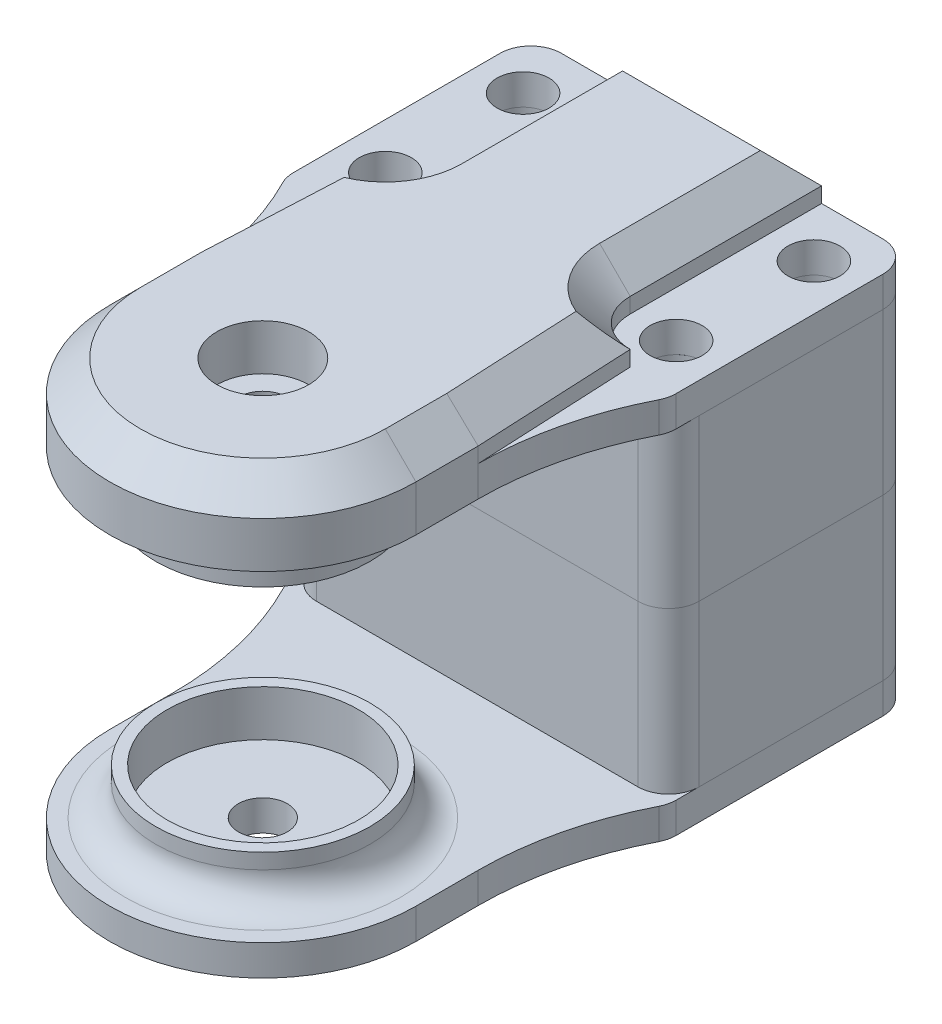
SolidWorks part; units mm, degrees
ref_plane "前视基准面" through (0, 0, 0) normal (0, 0, 1) x (1, 0, 0)
ref_plane "上视基准面" through (0, 0, 0) normal (0, 1, 0) x (1, 0, 0)
ref_plane "右视基准面" through (0, 0, 0) normal (1, 0, 0) x (0, 0, -1)
sketch "草图2" plane through (0, 0, 0) normal (0, 1, 0) x (1, 0, 0)
  circle A0 centre (0, 0) radius 10
  dimension "D1" = 20
extrude "凸台-拉伸1" add sketch "草图2" along normal blind 2
sketch "草图3" plane through (0, 2, 0) normal (0, 1, 0) x (1, 0, 0)
  line L0 (0, 8) -> (0, -8) construction
  circle A0 centre (0, 0) radius 6.25
  circle A1 centre (0, 0) radius 7
  dimension "D1" = 12.5
  dimension "D2" = 14
extrude "凸台-拉伸2" add sketch "草图3" along normal blind 3
sketch "草图4" plane through (0, 2, 0) normal (0, 1, 0) x (1, 0, 0)
  circle A0 centre (0, 0) radius 1.6
  dimension "D1" = 3.2
extrude "切除-拉伸1" cut sketch "草图4" against normal up to next
sketch "草图6" plane through (0, 0, 0) normal (0, -1, 0) x (1, 0, 0)
  line L0 (-10, 0) -> (-10, -30)
  line L1 (-10, -30) -> (10, -30)
  line L2 (10, -30) -> (10, 0)
  circle A0 centre (0, 0) radius 1.6 construction
  circle A1 centre (0, 0) radius 1.6
  circle A3 centre (0, 0) radius 10
  arc A4 (10, 0) -> (-10, 0) centre (0, 0) ccw
  dimension "D2" = 30
  dimension "D1" = 0
extrude "凸台-拉伸3" add sketch "草图6" against normal blind 2
sketch "草图11" plane through (0, 0, 0) normal (0, -1, 0) x (1, 0, 0)
  line L0 (0, -30) -> (0, -5.5094) construction
  line L1 (-10, -30) -> (10, -30) construction
  line L3 (-12.5, -14) -> (12.5, -14)
  line L4 (-12.5, -14) -> (-12.5, -30)
  line L5 (-12.5, -30) -> (12.5, -30)
  line L6 (12.5, -14) -> (12.5, -30)
  line L7 (-12.5, -14) -> (12.5, -30) construction
  line L8 (-12.5, -30) -> (12.5, -14) construction
  point P5 (0, -22)
  dimension "D1" = 25
  dimension "D2" = 16
extrude "凸台-拉伸6" add sketch "草图11" against normal up to surface (2 mm away) up to face at (0, 2, 7)
sketch "草图12" plane through (0, 2, 0) normal (0, 1, 0) x (1, 0, 0)
  line L1 (-12.5, 30) -> (12.5, 30)
  line L2 (-12.5, 30) -> (-12.5, 14)
  line L3 (-12.5, 14) -> (12.5, 14)
  line L4 (12.5, 30) -> (12.5, 14)
extrude "凸台-拉伸7" add sketch "草图12" along normal blind 21 separate body
sketch "草图13" plane through (0, 0, -30) normal (0, 0, -1) x (-1, 0, 0)
  line L0 (-12.5, 12.5) -> (12.5, 12.5) construction
  line L1 (-12.5, 23) -> (-12.5, 2) construction
  line L2 (12.5, 23) -> (12.5, 2) construction
  line L3 (0, 23) -> (0, 2) construction
  line L4 (-12.5, 23) -> (12.5, 23) construction
  line L5 (-12.5, 2) -> (12.5, 2) construction
  circle A0 centre (0, 12.5) radius 6.25
  dimension "D1" = 12.5
extrude "切除-拉伸4" cut sketch "草图13" against normal blind 13
sketch "草图14" plane through (0, 23, 0) normal (0, 1, 0) x (1, 0, 0)
  line L0 (0, 30) -> (0, 14) construction
  line L1 (12.5, 30) -> (-12.5, 30) construction
  line L2 (-12.5, 14) -> (12.5, 14) construction
  line L3 (-12.5, 22) -> (12.5, 22) construction
  line L4 (-12.5, 30) -> (-12.5, 14) construction
  line L5 (12.5, 14) -> (12.5, 30) construction
  circle A0 centre (9.5, 26.5) radius 1.7
  circle A1 centre (-9.5, 26.5) radius 1.7
  circle A2 centre (9.5, 17.5) radius 1.7
  circle A3 centre (-9.5, 17.5) radius 1.7
  dimension "D1" = 3.4
  dimension "D2" = 19
  dimension "D3" = 9
extrude "切除-拉伸5" cut sketch "草图14" against normal through all
fillet "圆角4" radius 21 2 edges at (-10, 1, -14) (10, 1, -14)
fillet "圆角5" radius 2 4 edges at (-12.5, 1, -14) (-12.5, 1, -30) (12.5, 1, -30) (12.5, 1, -14)
fillet "圆角6" radius 2 4 edges at (12.5, 12.5, -30) (12.5, 12.5, -14) (-12.5, 12.5, -30) (-12.5, 12.5, -14)
chamfer "倒角1" distance 0.5 angle 45 1 edges at (-6.25, 12.5, -30)
fillet "圆角7" radius 2 1 edges at (0, 2, 7)
ref_plane "基准面2" through (0, 12.5, 0) normal (0, 1, 0) x (1, 0, 0)
mirror "镜向2" about plane through (0, 12.5, 0) normal (0, 1, 0) of bodies 122
split "分割2" trim tools "基准面2" bodies to split 123 resulting bodies 125 126
sketch "草图15" plane through (0, 25, 0) normal (0, 1, 0) x (1, 0, 0)
  line L0 (0, 27.8447) -> (0, -7.0253) construction
  line L1 (-9.5, 20.5) -> (-9.5, 23.5)
  line L2 (-9.5, 29.5) -> (-9.5, 30)
  line L3 (9.5, 20.5) -> (9.5, 23.5)
  line L4 (9.5, 29.5) -> (9.5, 30)
  line L5 (6.5, 26.5) -> (6.5, 30)
  line L6 (-10, 4.0627) -> (-10, 0)
  line L7 (10, 0) -> (10, 4.0627)
  line L8 (12.5, 14.491) -> (12.5, 28)
  line L9 (10.5, 30) -> (-10.5, 30)
  line L10 (-12.5, 28) -> (-12.5, 14.491)
  line L11 (-10, 4.0627) -> (-10, 0)
  line L12 (10, 0) -> (10, 4.0627)
  line L14 (9.5, 30) -> (-9.5, 30)
  line L16 (-10, 4.0627) -> (-9.5, 14.5)
  line L17 (10, 4.0627) -> (9.5, 14.5)
  line L18 (-6.5, 26.5) -> (-6.5, 30)
  line L19 (-6.5, 26.5) -> (-6.5, 17.5)
  line L20 (6.5, 17.5) -> (6.5, 26.5)
  circle A0 centre (-9.5, 17.5) radius 3
  circle A1 centre (-9.5, 26.5) radius 3
  circle A2 centre (9.5, 26.5) radius 3
  circle A3 centre (9.5, 17.5) radius 3
  circle A4 centre (0, 0) radius 3
  arc A12 (-10, 4.0627) -> (-12.2826, 13.5842) centre (-31, 4.0627) ccw
  arc A13 (-10, 0) -> (10, 0) centre (0, 0) ccw
  arc A14 (12.2826, 13.5842) -> (10, 4.0627) centre (31, 4.0627) ccw
  arc A15 (12.2826, 13.5842) -> (12.5, 14.491) centre (10.5, 14.491) ccw
  arc A16 (12.5, 28) -> (10.5, 30) centre (10.5, 28) ccw
  arc A17 (-10.5, 30) -> (-12.5, 28) centre (-10.5, 28) ccw
  arc A18 (-12.5, 14.491) -> (-12.2826, 13.5842) centre (-10.5, 14.491) ccw
  arc A20 (-10, 0) -> (10, 0) centre (0, 0) ccw
  dimension "D1" = 6
  dimension "D2" = 0
extrude "凸台-拉伸9" add sketch "草图15" along normal blind 3 contours A3 L3 A2 L4 L2 A1 L1 A0 A4 region at (0, 25, -9.5651)
chamfer "倒角2" distance 2 angle 45 10 edges at (7.3787, 28, -15.3787) (9.75, 28, -9.2813) (-7.3787, 28, -15.3787) (-9.75, 28, -9.2813) (6.5, 28, -23.75) (-6.5, 28, -23.75) (-10, 28, -2.0313) (10, 28, -2.0313) (0, 28, 10) (0, 28, -30)
